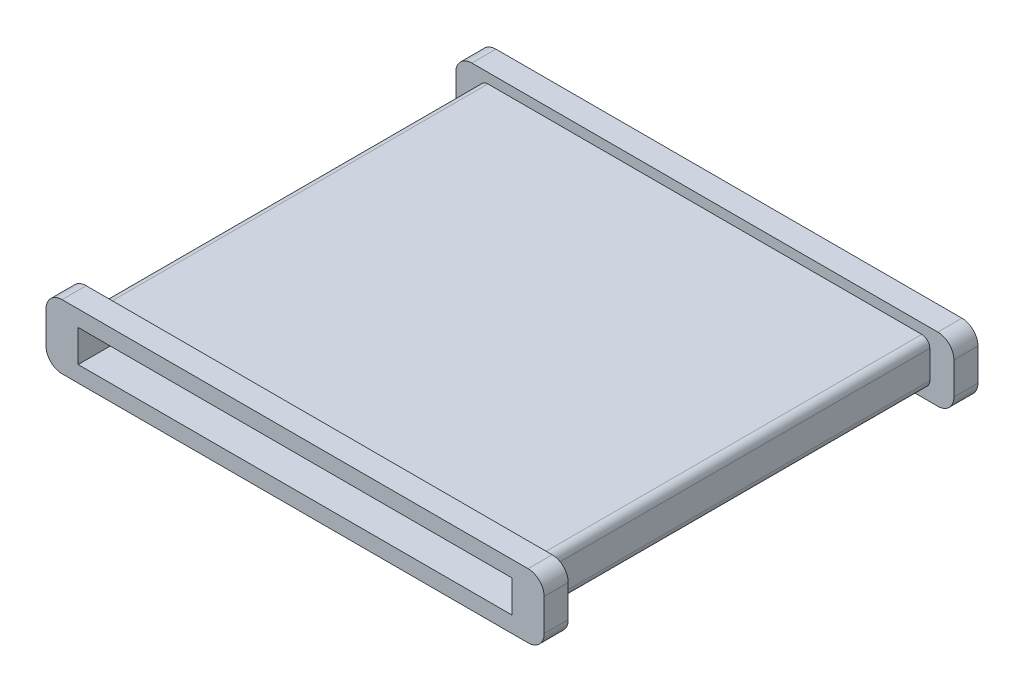
SolidWorks part; units mm, degrees
material "ABS"
ref_plane "Front Plane" through (0, 0, 0) normal (0, 0, 1) x (1, 0, 0)
ref_plane "Top Plane" through (0, 0, 0) normal (0, 1, 0) x (1, 0, 0)
ref_plane "Right Plane" through (0, 0, 0) normal (1, 0, 0) x (0, 0, -1)
sketch "Sketch1" plane through (0, 0, 0) normal (0, 0, 1) x (1, 0, 0)
  line L0 (0, 8) -> (62, 8)
  line L3 (62, 8) -> (62, 0)
  line L4 (62, 0) -> (0, 0)
  line L5 (0, 0) -> (0, 8)
  line L9 (4, 6) -> (58, 6)
  line L10 (4, 6) -> (4, 2)
  line L11 (4, 2) -> (58, 2)
  line L12 (58, 6) -> (58, 2)
  dimension "D1" = 2
  dimension "D2" = 54
  dimension "D4" = 4
  dimension "D5" = 2
  dimension "D7" = 4
  dimension "D8" = 4
extrude "Boss-Extrude1" add sketch "Sketch1" along normal blind 54
sketch "Sketch2" plane through (0, 0, 54) normal (0, 0, 1) x (1, 0, 0)
  line L0 (0, 8) -> (0, 0) construction
  line L1 (4, 6.75) -> (58, 6.75)
  line L2 (3, 5.75) -> (3, 2.25)
  line L3 (4, 1.25) -> (58, 1.25)
  line L4 (59, 5.75) -> (59, 2.25)
  line L5 (4, 2) -> (58, 2) construction
  line L7 (62, 0) -> (62, 8) construction
  arc A0 (3, 2.25) -> (4, 1.25) centre (4, 2.25) ccw
  arc A1 (58, 1.25) -> (59, 2.25) centre (58, 2.25) ccw
  arc A2 (58, 6.75) -> (59, 5.75) centre (58, 5.75) cw
  arc A3 (4, 6.75) -> (3, 5.75) centre (4, 5.75) ccw
  dimension "D1" = 1
  dimension "D2" = 5.5
  dimension "D3" = 3
  dimension "D4" = 3
  dimension "D5" = 0.75
extrude "Cut-Extrude1" cut sketch "Sketch2" against normal offset from surface (48 mm away) 3 from offset 3 flip side to cut up to face at (31, 4, 0) offset against normal yes
fillet "Fillet1" radius 2 8 edges at (62, 8, 52.5) (62, 0, 52.5) (62, 0, 1.5) (62, 8, 1.5) (0, 0, 1.5) (0, 8, 1.5) (0, 0, 52.5) (0, 8, 52.5)
